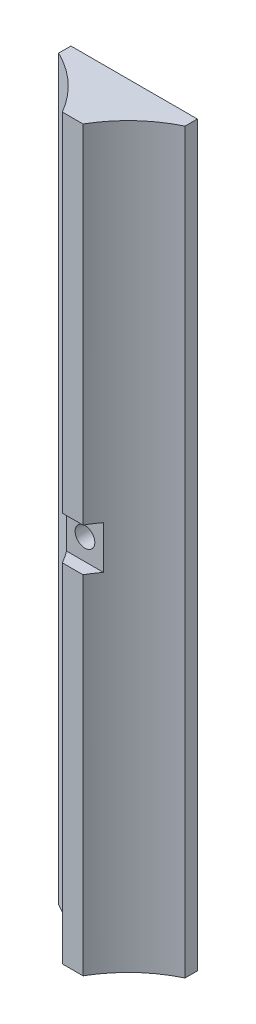
SolidWorks part; units mm, degrees
material "6061-T6 (SS)"
ref_plane "Front" through (0, 0, 0) normal (0, 0, 1) x (1, 0, 0)
ref_plane "Top" through (0, 0, 0) normal (0, 1, 0) x (1, 0, 0)
ref_plane "Right" through (0, 0, 0) normal (1, 0, 0) x (0, 0, -1)
sketch "Sketch1" plane through (0, 0, 0) normal (0, 1, 0) x (1, 0, 0)
  line L0 (-0.8397, 0) -> (0.8397, 0)
  line L1 (5.1411, 4) -> (5.1411, 5)
  line L2 (5.1411, 5) -> (-5.1411, 5)
  line L3 (-5.1411, 5) -> (-5.1411, 4)
  arc A0 (0.8397, 0) -> (5.1411, 4) centre (9.5, -5) cw
  arc A1 (-5.1411, 4) -> (-0.8397, 0) centre (-9.5, -5) cw
  point P9 (0, 5)
  point P10 (0, 0)
  dimension "D1" = 10
  dimension "D6" = 5
  dimension "D2" = 19
  dimension "D3" = 10
  dimension "D4" = 1
extrude "Boss-Extrude1" add sketch "Sketch1" along normal mid plane 60
sketch "Sketch3" plane through (0, 0, -5) normal (0, 0, -1) x (-1, 0, 0)
  line L0 (0, -30) -> (0, 30) construction
  line L1 (-5.1411, -30) -> (5.1411, -30) construction
  line L2 (-5.1411, 30) -> (5.1411, 30) construction
  point P6 (0, 0)
  dimension "D2" = 30
hole_wizard "M2x0.4 Tapped Hole1" positions "3DSketch1" profile "Sketch4" tap size "M2x0.4" standard "ANSI Metric" end condition through all
sketch3d "3DSketch1"
  point P0 (0, 0, -5)
cosmetic thread "Hole Thread2" parameters "D2"=2
sketch "Sketch4" plane through (0, 0, -5) normal (1, 0, 0) x (0, 1, 0)
  line L0 (0, 0) -> (0, 5)
  line L1 (0, 5) -> (0.8, 5)
  line L2 (0.8, 5) -> (0.8, 0)
  line L5 (0.8, 0) -> (0, 0)
  line L11 (0, -6.35) -> (0, 107.95) construction
  dimension "Thru Tap Drill Dia." = 1.6
  dimension "Thru Tap Drill Depth" = 5
sketch "Sketch7" plane through (0, 0, 0) normal (0, 0, 1) x (1, 0, 0)
  line L0 (-5.1411, 30) -> (-5.1411, -30) construction
  line L1 (-5.1411, -1.75) -> (4.4212, -1.75)
  line L2 (-5.1411, -1.75) -> (-5.1411, 1.75)
  line L3 (-5.1411, 1.75) -> (4.4212, 1.75)
  line L4 (4.4212, -1.75) -> (4.4212, 1.75)
  point P4 (-5.1411, 0)
  point P7 (-5.1411, 0)
  dimension "D1" = 3.5
extrude "Cut-Extrude1" cut sketch "Sketch7" against normal blind 1
